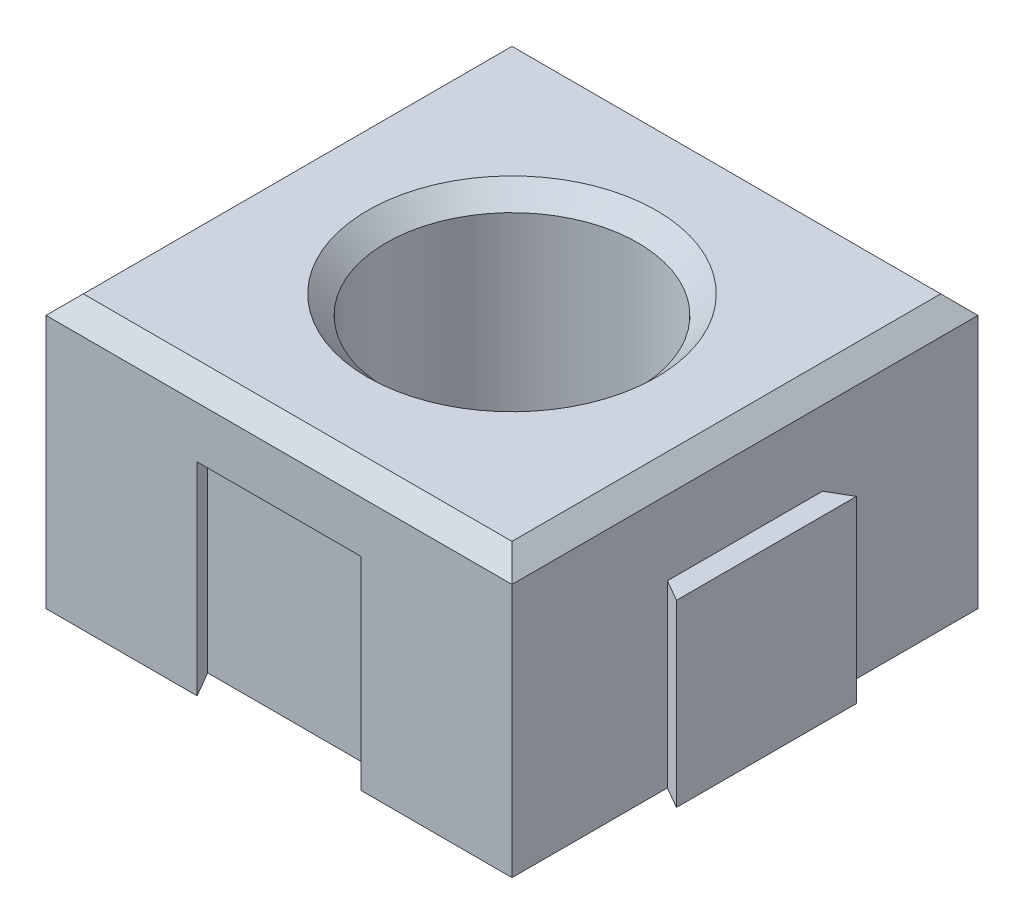
SolidWorks part; units mm, degrees
ref_plane "Front Plane" through (0, 0, 0) normal (0, 0, 1) x (1, 0, 0)
ref_plane "Top Plane" through (0, 0, 0) normal (0, 1, 0) x (1, 0, 0)
ref_plane "Right Plane" through (0, 0, 0) normal (1, 0, 0) x (0, 0, -1)
sketch "Sketch1" plane through (0, 0, 0) normal (0, 1, 0) x (1, 0, 0)
  line L1 (0, 0) -> (50, 0)
  line L2 (0, 0) -> (0, 50)
  line L3 (0, 50) -> (50, 50)
  line L4 (50, 0) -> (50, 50)
  dimension "D1" = 50
extrude "Boss-Extrude1" add sketch "Sketch1" along normal blind 30
sketch "Sketch2" plane through (0, 30, 0) normal (0, 1, 0) x (1, 0, 0)
  line L0 (0, 0) -> (50, 50) construction
  line L1 (0, 50) -> (50, 0) construction
  circle A0 centre (25, 25) radius 13.5
  dimension "D1" = 27
extrude "Cut-Extrude1" cut sketch "Sketch2" against normal blind 26
sketch "Sketch3" plane through (0, 0, 0) normal (0, 1, 0) x (1, 0, 0)
  line L0 (50, 33.5566) -> (52.5, 35) construction
  line L1 (50, 0) -> (50, 50) construction
  line L2 (52.5, 35) -> (52.5, 15) construction
  line L3 (52.5, 15) -> (50, 16.4434) construction
  line L4 (50, 25) -> (52.5, 25) construction
  line L5 (16.4434, 50) -> (15, 52.5) construction
  line L6 (50, 50) -> (0, 50) construction
  line L7 (15, 52.5) -> (35, 52.5) construction
  line L8 (35, 52.5) -> (33.5566, 50) construction
  line L9 (25, 52.5) -> (25, 50) construction
  line L10 (0, 33.5566) -> (2.5, 35) construction
  line L11 (0, 50) -> (0, 0) construction
  line L12 (2.5, 35) -> (2.5, 15) construction
  line L13 (2.5, 15) -> (0, 16.4434) construction
  line L14 (0, 25) -> (2.5, 25) construction
  line L15 (16.4434, 0) -> (15, 2.5) construction
  line L16 (0, 0) -> (50, 0) construction
  line L17 (15, 2.5) -> (35, 2.5) construction
  line L18 (35, 2.5) -> (33.5566, 0) construction
  line L19 (25, 0) -> (25, 2.5) construction
  line L20 (50, 16.6743) -> (50, 33.3257)
  line L21 (33.3257, 50) -> (16.6743, 50)
  line L23 (16.4434, 0) -> (33.5566, 0) construction
  line L24 (50, 33.3257) -> (52.3, 34.6536)
  line L25 (52.3, 34.6536) -> (52.3, 15.3464)
  line L26 (52.3, 15.3464) -> (50, 16.6743)
  line L27 (52.3, 34.6536) -> (52.2, 34.8268) construction
  line L28 (16.2124, 0) -> (14.6536, 2.7)
  line L29 (52.3, 34.6536) -> (52.5, 34.6536) construction
  line L30 (14.6536, 2.7) -> (35.3464, 2.7)
  line L31 (35.3464, 2.7) -> (33.7876, 0)
  line L32 (33.7876, 0) -> (16.2124, 0)
  line L33 (35, 2.5) -> (35, 2.7) construction
  line L34 (35, 2.5) -> (35.1732, 2.4) construction
  line L35 (0, 33.7876) -> (2.7, 35.3464)
  line L36 (2.7, 35.3464) -> (2.7, 14.6536)
  line L37 (2.7, 14.6536) -> (0, 16.2124)
  line L38 (0, 16.2124) -> (0, 33.7876)
  line L39 (2.4, 14.8268) -> (2.5, 15) construction
  line L40 (2.5, 15) -> (2.7, 15) construction
  line L41 (16.6743, 50) -> (15.3464, 52.3)
  line L42 (15.3464, 52.3) -> (34.6536, 52.3)
  line L43 (34.6536, 52.3) -> (33.3257, 50)
  line L44 (15.3464, 52.5) -> (15.3464, 52.3) construction
  line L45 (15.1732, 52.2) -> (15.3464, 52.3) construction
  point P8 (50, 25)
  point P39 (52.3, 25)
  point P40 (25, 0)
  point P53 (0, 25)
  point P59 (25, 52.3)
  point P61 (51.9996, 34.4222)
  point P63 (25, 50)
  dimension "D1" = 0.2
  dimension "D2" = 60
  dimension "D3" = 2.5
  dimension "D4" = 20
extrude "Boss-Extrude2" add sketch "Sketch3" along normal blind 20 contours L20 L24 L25 L26
extrude "Boss-Extrude3" add sketch "Sketch3<3>" along normal blind 20 contours L21 L41 L42 L43
sketch "Sketch3<3>" plane through (0, 0, 0) normal (0, 1, 0) x (1, 0, 0) same geometry as "Sketch3"
extrude "Cut-Extrude5" cut sketch "Sketch3<6>" along normal blind 20 contours L38 L35 L36 L37
sketch "Sketch3<6>" plane through (0, 0, 0) normal (0, 1, 0) x (1, 0, 0) same geometry as "Sketch3"
extrude "Cut-Extrude6" cut sketch "Sketch3<7>" along normal blind 20 contours L32 L28 L30 L31
sketch "Sketch3<7>" plane through (0, 0, 0) normal (0, 1, 0) x (1, 0, 0) same geometry as "Sketch3"
chamfer "Chamfer1" distance 2 angle 45 5 edges at (25, 30, -50) (50, 30, -25) (25, 30, 0) (0, 30, -25) (25, 30, -11.5)
sketch "Sketch4" plane through (0, 0, 0) normal (0, 1, 0) x (1, 0, 0)
  line L0 (12.5, 12.5) -> (37.5, 37.5) construction
  line L1 (12.5, 12.5) -> (37.5, 12.5) construction
  line L2 (12.5, 12.5) -> (12.5, 37.5) construction
  line L3 (12.5, 37.5) -> (37.5, 37.5) construction
  line L4 (37.5, 12.5) -> (37.5, 37.5) construction
  line L5 (12.5, 37.5) -> (37.5, 12.5) construction
  line L6 (0, 0) -> (12.5, 12.5) construction
  line L7 (12.5, 37.5) -> (0, 50) construction
  line L8 (50, 50) -> (37.5, 37.5) construction
  line L9 (50, 0) -> (37.5, 12.5) construction
  line L10 (0, 25) -> (25, 25) construction
  circle A0 centre (12.5, 37.5) radius 3.1
  circle A1 centre (37.5, 37.5) radius 3.1
  circle A2 centre (37.5, 12.5) radius 3.1
  circle A3 centre (12.5, 12.5) radius 3.1
  point P15 (12.5, 25)
  dimension "D1" = 6.2
extrude "Cut-Extrude4" cut sketch "Sketch4" along normal blind 4
chamfer "Chamfer2" distance 1 angle 45 4 edges at (37.5, 4, -9.4) (12.5, 4, -9.4) (12.5, 4, -34.4) (37.5, 4, -34.4)
chamfer "Chamfer3" distance 0.75 angle 45 24 edges at (41.8938, 0, 0) (50, 0, -8.3372) (50, 0, -41.6628) (41.6628, 0, -50) (8.3372, 0, -50) (0, 0, -41.8938) (0, 0, -8.1062) (8.1062, 0, 0) (12.5, 0, -34.4) (37.5, 0, -34.4) (37.5, 0, -9.4) (12.5, 0, -9.4) (51.15, 0, -16.0104) (52.3, 0, -25) (51.15, 0, -33.9896) (33.9896, 0, -51.15) (25, 0, -52.3) (16.0104, 0, -51.15) (1.35, 0, -34.567) (2.7, 0, -25) (1.35, 0, -15.433) (15.433, 0, -1.35) (25, 0, -2.7) (34.567, 0, -1.35)
chamfer "Chamfer4" distance 2.5 angle 45 2 edges at (25, 20, 0) (0, 20, -25)
